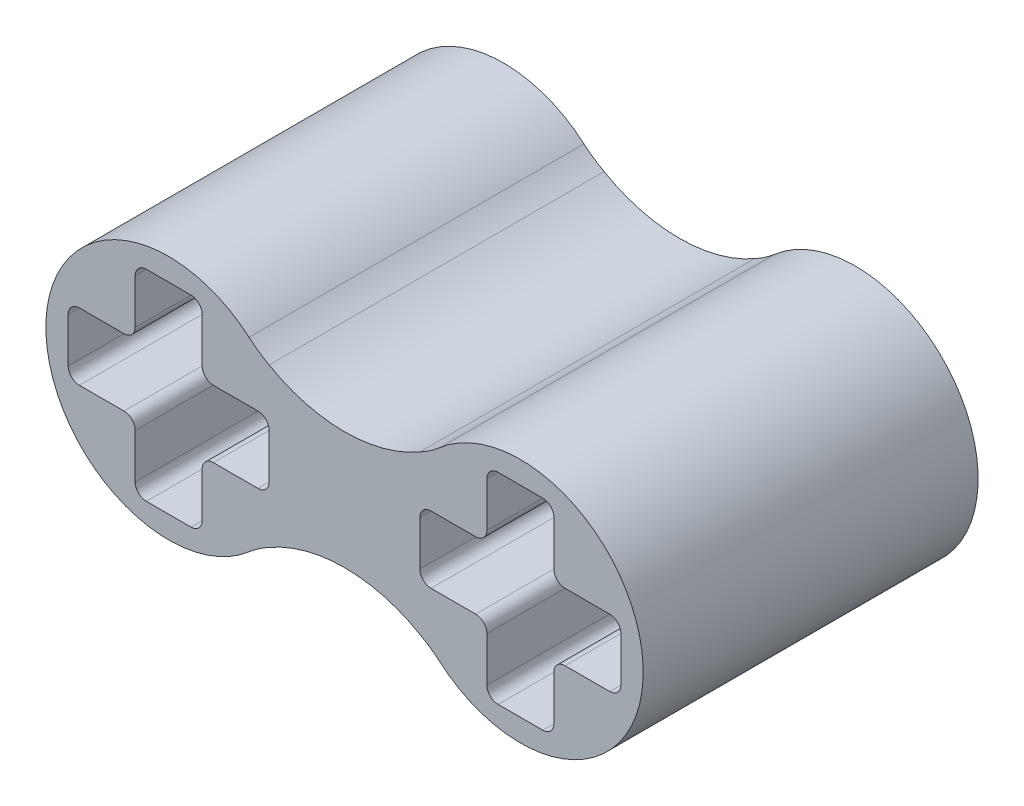
SolidWorks part; units mm, degrees
material "ABS PC"
ref_plane "Front Plane" through (0, 0, 0) normal (0, 0, 1) x (1, 0, 0)
ref_plane "Top Plane" through (0, 0, 0) normal (0, 1, 0) x (1, 0, 0)
ref_plane "Right Plane" through (0, 0, 0) normal (1, 0, 0) x (0, 0, -1)
sketch "Sketch2" plane through (0, 0, 0) normal (0, 0, 1) x (1, 0, 0)
  circle A0 centre (0, 0) radius 2.794
  dimension "D1" = 5.588
extrude "Extrude1" add sketch "Sketch2" along normal blind 7.62
sketch "Sketch3" plane through (0, 0, 7.62) normal (0, 0, 1) x (1, 0, 0)
  line L0 (-0.762, 2.032) -> (-0.762, 1.016)
  line L1 (-1.016, 0.762) -> (-2.032, 0.762)
  line L2 (-2.286, 0.508) -> (-2.286, -0.508)
  line L3 (-2.032, -0.762) -> (-1.016, -0.762)
  line L4 (-0.762, -1.016) -> (-0.762, -2.032)
  line L5 (-0.508, -2.286) -> (0.508, -2.286)
  line L6 (0.762, -2.032) -> (0.762, -1.016)
  line L7 (1.016, -0.762) -> (2.032, -0.762)
  line L8 (2.286, -0.508) -> (2.286, 0.508)
  line L9 (2.032, 0.762) -> (1.016, 0.762)
  line L10 (0.762, 1.016) -> (0.762, 2.032)
  line L11 (0.508, 2.286) -> (-0.508, 2.286)
  line L12 (0, -18.7166) -> (0, 18.7166) construction
  line L13 (35.7523, 0) -> (-35.7523, 0) construction
  arc A0 (-0.762, 1.016) -> (-1.016, 0.762) centre (-1.016, 1.016) cw
  arc A1 (-0.762, 2.032) -> (-0.508, 2.286) centre (-0.508, 2.032) cw
  arc A2 (0.508, 2.286) -> (0.762, 2.032) centre (0.508, 2.032) cw
  arc A3 (0.762, 1.016) -> (1.016, 0.762) centre (1.016, 1.016) ccw
  arc A4 (2.032, 0.762) -> (2.286, 0.508) centre (2.032, 0.508) cw
  arc A5 (2.032, -0.762) -> (2.286, -0.508) centre (2.032, -0.508) ccw
  arc A6 (1.016, -0.762) -> (0.762, -1.016) centre (1.016, -1.016) ccw
  arc A7 (0.762, -2.032) -> (0.508, -2.286) centre (0.508, -2.032) cw
  arc A8 (-0.508, -2.286) -> (-0.762, -2.032) centre (-0.508, -2.032) cw
  arc A9 (-1.016, -0.762) -> (-0.762, -1.016) centre (-1.016, -1.016) cw
  arc A10 (-2.032, -0.762) -> (-2.286, -0.508) centre (-2.032, -0.508) cw
  arc A11 (-2.286, 0.508) -> (-2.032, 0.762) centre (-2.032, 0.508) cw
  point P40 (0, 0)
  dimension "D6" = 0.254
  dimension "D1" = 4.572
  dimension "D2" = 4.572
  dimension "D3" = 1.524
  dimension "D4" = 1.524
  dimension "D5" = 1.524
extrude "Cut-Extrude1" cut sketch "Sketch3" against normal through all
sketch "Sketch4" plane through (0, 0, 7.62) normal (0, 0, 1) x (1, 0, 0)
  line L0 (0, 0) -> (8.001, 0)
  dimension "D1" = 8.001
pattern_linear "LPattern1" count 2 spacing 8.001 along (1, 0, 0) of bodies 102
sketch "Sketch5" plane through (0, 0, 7.62) normal (0, 0, 1) x (1, 0, 0)
  line L1 (0, 0) -> (8.001, 0) construction
  line L2 (2.286, 1.7973) -> (2.286, -1.7973)
  line L3 (5.715, 1.7973) -> (5.715, -1.7973)
  line L4 (5.715, 0.508) -> (5.715, -0.508) construction
  line L5 (2.286, -0.508) -> (2.286, 0.508) construction
  arc A0 (2.286, 1.7973) -> (5.715, 1.7973) centre (4.0005, 4.7684) ccw
  arc A1 (5.715, -1.7973) -> (2.286, -1.7973) centre (4.0005, -4.7684) ccw
  circle A3 centre (8.001, 0) radius 2.794 construction
  circle A4 centre (0, 0) radius 2.794 construction
extrude "Extrude3" add sketch "Sketch5" against normal through all
fillet "Fillet1" radius 2.54 4 edges at (2.286, -1.6064, 3.81) (5.715, -1.6064, 3.81) (2.286, 1.6064, 3.81) (5.715, 1.6064, 3.81)
